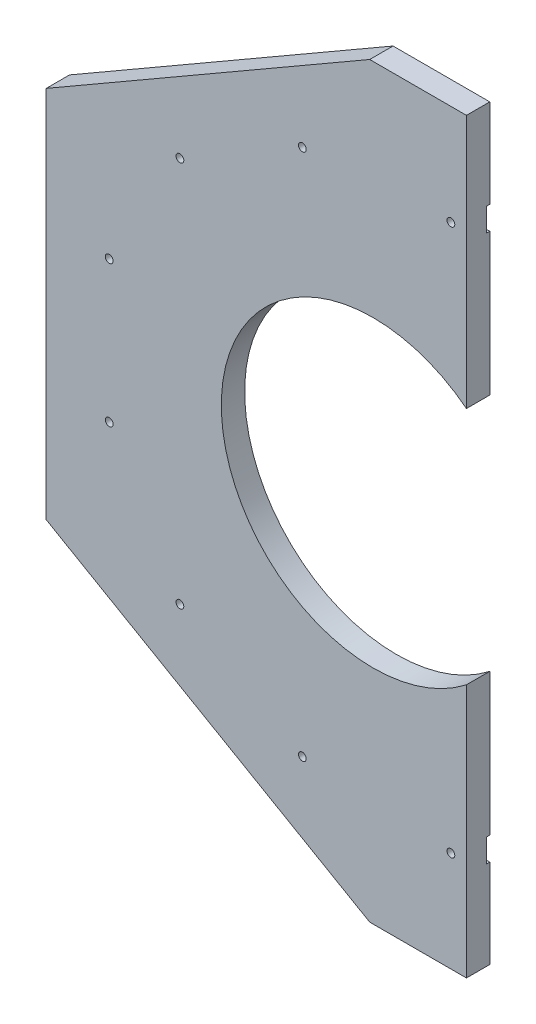
SolidWorks part; units mm, degrees
note: The reader was unsure of these and kept them because the rebuilt part matched: shared geometry of "草图1<4>".
material "A6061"
ref_plane "前视基准面" through (0, 0, 0) normal (0, 0, 1) x (1, 0, 0)
ref_plane "上视基准面" through (0, 0, 0) normal (0, 1, 0) x (1, 0, 0)
ref_plane "右视基准面" through (0, 0, 0) normal (1, 0, 0) x (0, 0, -1)
sketch "草图1" plane through (0, 0, 0) normal (0, 0, 1) x (1, 0, 0)
  line L0 (-143.2729, 0) -> (135.0694, 0) construction
  line L1 (140, 240) -> (-140, 240)
  line L2 (140, 240) -> (140, -240)
  line L3 (140, -240) -> (-140, -240)
  line L4 (-140, 240) -> (-140, -240)
  line L5 (140, 240) -> (-140, -240) construction
  line L6 (140, -240) -> (-140, 240) construction
  line L7 (80, 183) -> (80, -183) construction
  line L8 (80, -183) -> (244.5668, -183)
  line L9 (80, -168) -> (244.5668, -168)
  line L10 (244.5668, -168) -> (244.5668, -183)
  line L11 (80, 183) -> (244.3671, 183)
  line L12 (80, 168) -> (244.3671, 168)
  line L13 (244.3671, 168) -> (244.3671, 183)
  arc A1 (80, 168) -> (80, -168) centre (80, 0) ccw
  arc A2 (80, 183) -> (80, -183) centre (80, 0) ccw
  point P0 (0, 0)
  dimension "D3" = 183
  dimension "D4" = 336
  dimension "D1" = 480
  dimension "D2" = 280
  dimension "D5" = 220
  dimension "D6" = 37
extrude "凸台-拉伸1" add sketch "草图1" along normal blind 15 contours A2 L11 L2 L1 L4 L3 L8 | L12 A1 L9 L2 | L11 A2 L8 L2 L9 A1 L12
extrude "切除-拉伸2" cut sketch "草图1<4>" along normal blind 2 contours L11 A2 L8 L2 L9 A1 L12
sketch "草图1<4>" plane through (0, 0, 0) normal (0, 0, 1) x (1, 0, 0) same geometry as "草图1"
sketch "草图2" plane through (0, 0, 0) normal (0, 0, -1) x (-1, 0, 0)
  circle A0 centre (-80, 0) radius 97.5
  dimension "D1" = 195
extrude "切除-拉伸3" cut sketch "草图2" against normal through all
sketch "草图3" plane through (0, 0, 0) normal (0, 0, -1) x (-1, 0, 0)
  line L0 (-140, 240) -> (-77.8461, 240)
  line L1 (-140, 240) -> (140, 240) construction
  line L2 (-77.8461, 240) -> (130, 120)
  line L4 (130, 120) -> (130, -120)
  line L5 (130, -120) -> (-77.8461, -240)
  line L6 (-140, -240) -> (140, -240) construction
  line L7 (-77.8461, -240) -> (-140, -240)
  line L8 (140, 240) -> (140, -240) construction
  line L9 (0, 0) -> (169.5871, 0) construction
  point P6 (130, 0)
  dimension "D1" = 10
  dimension "D2" = 240
extrude "切除-拉伸4" cut sketch "草图3" against normal through all and the other way through all
sketch "草图4" plane through (0, 0, 2) normal (0, 0, -1) x (-1, 0, 0)
  line L0 (-80, 0) -> (-80, -175.5) construction
  line L1 (-80, 0) -> (-34.5773, -169.52) construction
  line L2 (-80, -175.5) -> (-151.9455, -175.5) construction
  line L3 (-140, -168) -> (-140, -183) construction
  line L4 (-164.3792, 0) -> (-49.4611, 0) construction
  circle A0 centre (-80, 0) radius 175.5 construction
  circle A1 centre (-34.5773, -169.52) radius 3
  circle A2 centre (-125.4227, -169.52) radius 3
  circle A3 centre (-204.0972, -124.0972) radius 3
  circle A4 centre (-249.52, -45.4227) radius 3
  circle A5 centre (-249.52, 45.4227) radius 3
  circle A6 centre (-204.0972, 124.0972) radius 3
  circle A7 centre (-125.4227, 169.52) radius 3
  circle A8 centre (-34.5773, 169.52) radius 3
  circle A9 centre (44.0972, 124.0972) radius 3
  circle A10 centre (89.52, 45.4227) radius 3
  circle A11 centre (89.52, -45.4227) radius 3
  circle A12 centre (44.0972, -124.0972) radius 3
  circle A13 centre (-130, -175.5) radius 2.9903
  circle A14 centre (-130, 175.5) radius 2.9903
  point P31 (-80, 0)
  dimension "D1" = 351
  dimension "D3" = 6
  dimension "D2" = 15
  dimension "D5" = 10
  dimension "D4" = 12
hole_wizard "M6 螺纹孔1" positions "草图5" profile "草图6" tap size "M6" standard "GB" end condition through all
sketch "草图5" plane through (0, 0, 2) normal (0, 0, -1) x (-1, 0, 0)
  point P0 (-34.5773, -169.52)
  point P3 (44.0972, -124.0972)
  point P6 (89.52, -45.4227)
  point P9 (89.52, 45.4227)
  point P12 (44.0972, 124.0972)
  point P15 (-34.5773, 169.52)
  point P18 (-130, 175.5)
  point P21 (-130, -175.5)
sketch "草图6" plane through (34.5773, -169.52, 2) normal (1, 0, 0) x (0, 1, 0)
  line L0 (0, 0) -> (0, 13)
  line L1 (0, 13) -> (2.5, 13)
  line L2 (2.5, 13) -> (2.5, 0)
  line L5 (2.5, 0) -> (0, 0)
  line L11 (0, -6.35) -> (0, 107.95) construction
  dimension "通孔螺纹孔钻头直径" = 5
  dimension "通孔螺纹孔钻头深度" = 13
cosmetic thread "孔螺蚊线1" parameters "D2"=6
cosmetic thread "孔螺蚊线2" parameters "D2"=6
cosmetic thread "孔螺蚊线3" parameters "D2"=6
cosmetic thread "孔螺蚊线4" parameters "D2"=6
cosmetic thread "孔螺蚊线5" parameters "D2"=6
cosmetic thread "孔螺蚊线6" parameters "D2"=6
cosmetic thread "孔螺蚊线7" parameters "D2"=6
cosmetic thread "孔螺蚊线8" parameters "D2"=6
